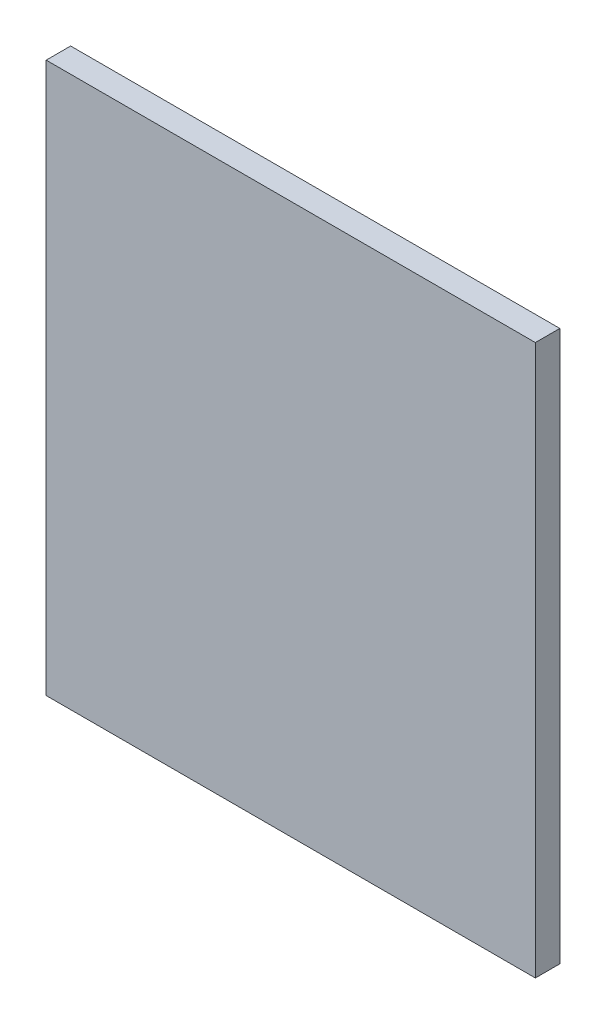
SolidWorks part; units mm, degrees
ref_plane "Front" through (0, 0, 0) normal (0, 0, 1) x (1, 0, 0)
ref_plane "Top" through (0, 0, 0) normal (0, 1, 0) x (1, 0, 0)
ref_plane "Right" through (0, 0, 0) normal (1, 0, 0) x (0, 0, -1)
sketch "草图1" plane through (0, 0, 0) normal (0, 0, 1) x (1, 0, 0)
  line L0 (-41.5, 6) -> (-41.5, -37.45) construction
  line L1 (-46.3476, 3.6) -> (-36.6524, 3.6) construction
  line L2 (-48.1132, -32.4) -> (-34.8868, -32.4) construction
  line L4 (-36.5, -35.5) -> (-46.5, -35.5) construction
  line L5 (-57.5, -32.4) -> (-25.5, -32.4)
  line L6 (-25.5, -32.4) -> (-25.5, 3.6)
  line L7 (-25.5, 3.6) -> (-57.5, 3.6)
  line L8 (-57.5, 3.6) -> (-57.5, -32.4)
  arc A0 (-4.05, 0.0164) -> (-78.95, 0.0164) centre (-41.5, -114.1875) ccw construction
  arc A1 (-78.95, 0.0164) -> (-4.05, 0.0164) centre (-41.5, 0) ccw construction
  point P11 (-41.5, 2.6)
  point P14 (-41.5, -35.5)
  point P20 (-41.5, -32.4)
  dimension "D1" = 3.1
  dimension "D2" = 1
  dimension "D3" = 32
  dimension "D4" = 36
extrude "凸台-拉伸1" add sketch "草图1" along normal blind 0.8 and the other way blind 0.8
